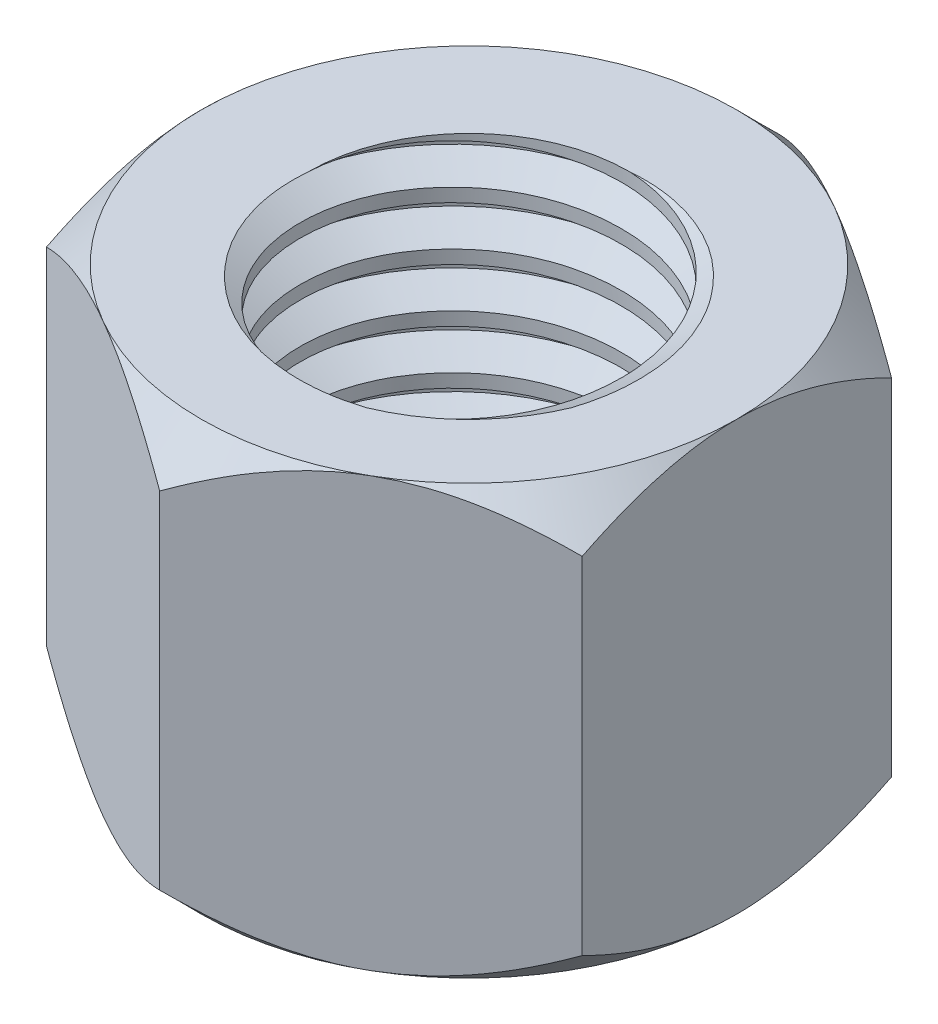
SolidWorks part; units mm, degrees
ref_plane "Front Plane" through (0, 0, 0) normal (0, 0, 1) x (1, 0, 0)
ref_plane "Top Plane" through (0, 0, 0) normal (0, 1, 0) x (1, 0, 0)
ref_plane "Right Plane" through (0, 0, 0) normal (1, 0, 0) x (0, 0, -1)
sketch "Sketch1" plane through (0, 0, 0) normal (0, 1, 0) x (1, 0, 0)
  line L1 (5, 2.8868) -> (0, 5.7735)
  line L2 (0, 5.7735) -> (-5, 2.8868)
  line L3 (-5, 2.8868) -> (-5, -2.8868)
  line L4 (-5, -2.8868) -> (0, -5.7735)
  line L5 (0, -5.7735) -> (5, -2.8868)
  line L6 (5, -2.8868) -> (5, 2.8868)
  circle A0 centre (0, 0) radius 5 construction
  circle A1 centre (0, 0) radius 3
  dimension "D2" = 6
  dimension "D1" = 10
extrude "Boss-Extrude1" add sketch "Sketch1" along normal mid plane 8
sketch "Sketch2" plane through (0, 4, 0) normal (0, 1, 0) x (1, 0, 0)
  circle A0 centre (0, 0) radius 5
  dimension "D1" = 10
extrude "Cut-Extrude1" cut sketch "Sketch2" against normal mid plane 8 draft 45 flip side to cut
mirror "Mirror1" about plane through (0, 0, 0) normal (0, 1, 0) of "Cut-Extrude1"
thread "Thread1" pitch 1 method cut profile "Thread Profile1" start angle 0, offset 3, length 30, pitch 1, diameter 6
ref_plane "Plane1" through (-3, 7, 0) normal (0, 0, 1) x (-1, 0, 0)
sketch "Thread Profile1" plane through (-3, 7, 0) normal (0, 0, 1) x (-1, 0, 0)
  line L0 (0, 0) -> (0, 1) construction
  line L1 (0, 0) -> (0.5413, 0.3125)
  line L2 (0.5413, 0.3125) -> (0.5413, 0.4375)
  line L3 (0.5413, 0.4375) -> (0, 0.75)
  line L4 (0.5413, 0.375) -> (0, 0.375) construction
  line L11 (0, 0) -> (0, 0.75)
  point P2 (0, 0)
  dimension "Pitch" = 1
  dimension "Profile_Angle" = 60
  dimension "Profile_Land" = 0.125
  dimension "Profile_Height" = 0.5413
